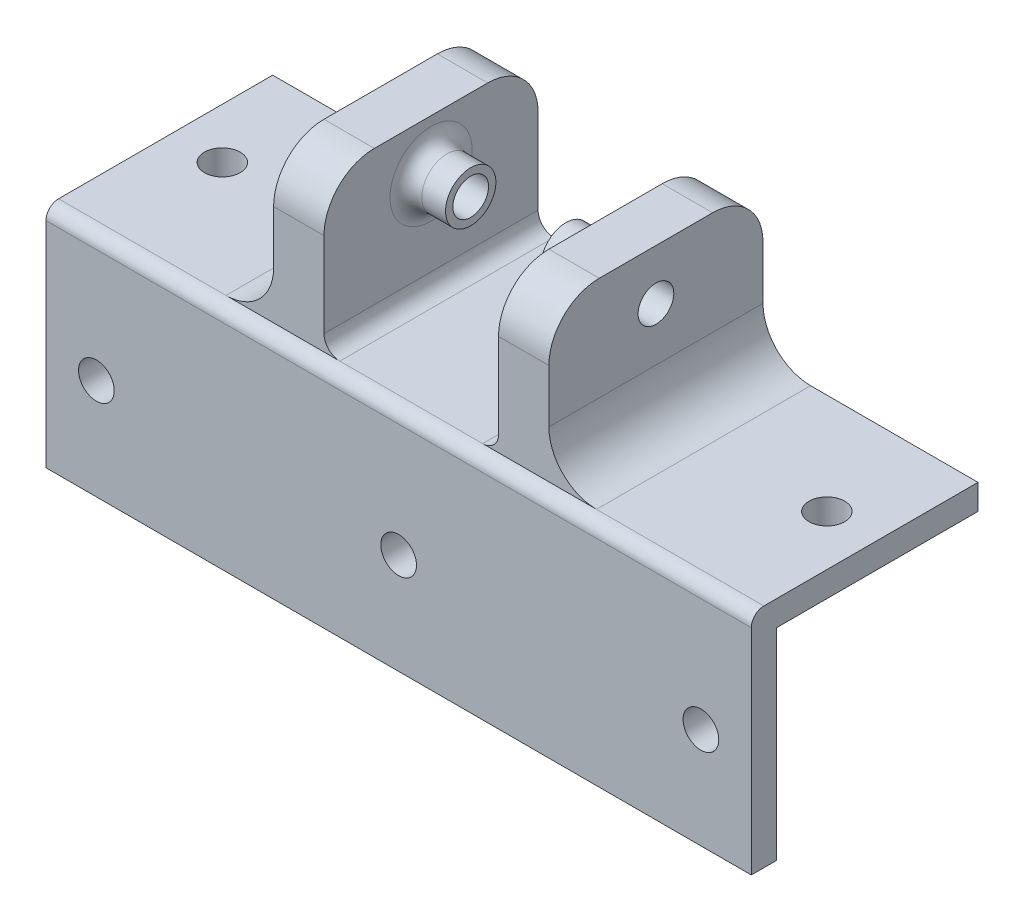
SolidWorks part; units mm, degrees
ref_plane "Front Plane" through (0, 0, 0) normal (0, 0, 1) x (1, 0, 0)
ref_plane "Top Plane" through (0, 0, 0) normal (0, 1, 0) x (1, 0, 0)
ref_plane "Right Plane" through (0, 0, 0) normal (1, 0, 0) x (0, 0, -1)
sketch "Sketch1" plane through (0, 0, 0) normal (0, 0, 1) x (1, 0, 0)
  line L1 (44.45, -12.7) -> (-44.45, -12.7)
  line L2 (44.45, -12.7) -> (44.45, 12.7)
  line L3 (44.45, 12.7) -> (-44.45, 12.7)
  line L4 (-44.45, -12.7) -> (-44.45, 12.7)
  line L5 (44.45, -12.7) -> (-44.45, 12.7) construction
  line L6 (44.45, 12.7) -> (-44.45, -12.7) construction
  circle A0 centre (0, 0) radius 2.25
  circle A1 centre (-38.1, 0) radius 2.25
  circle A2 centre (38.1, 0) radius 2.25
  point P0 (0, 0)
  point P12 (0, 0)
  point P13 (0, 0)
  dimension "D2" = 4.5
  dimension "D1" = 25.4
  dimension "D3" = 38.1
  dimension "D4" = 88.9
  dimension "D5" = 38.1
extrude "Boss-Extrude1" add sketch "Sketch1" along normal blind 3.175
sketch "Sketch2" plane through (0, 12.7, 0) normal (0, 1, 0) x (1, 0, 0)
  line L0 (44.45, 0) -> (-44.45, 0) construction
  line L1 (-44.45, -3.175) -> (44.45, -3.175)
  line L2 (-44.45, -3.175) -> (-44.45, 25.4)
  line L3 (-44.45, 25.4) -> (44.45, 25.4)
  line L4 (44.45, -3.175) -> (44.45, 25.4)
  circle A0 centre (0, 12.7) radius 2.25
  circle A1 centre (-38.1, 12.7) radius 2.25
  circle A2 centre (38.1, 12.7) radius 2.25
  point P14 (0, 12.7)
  point P16 (0, 0)
  dimension "D3" = 4.5
  dimension "D1" = 25.4
  dimension "D2" = 12.7
  dimension "D4" = 38.1
  dimension "D5" = 38.1
extrude "Boss-Extrude2" add sketch "Sketch2" along normal blind 3.175
fillet "Fillet1" radius 1.5875 1 edges at (0, 15.875, 3.175)
sketch "Sketch4" plane through (0, 15.875, 0) normal (0, 1, 0) x (1, 0, 0)
  line L0 (11, 12.7) -> (-11, 12.7)
  line L1 (44.45, 25.4) -> (-44.45, 25.4) construction
  line L2 (-11, 25.4) -> (-17.35, 25.4)
  line L3 (-11, 25.4) -> (-11, -1.5875)
  line L4 (-11, -1.5875) -> (-17.35, -1.5875)
  line L5 (-17.35, 25.4) -> (-17.35, -1.5875)
  line L6 (-44.45, -1.5875) -> (44.45, -1.5875) construction
  line L8 (11, 25.4) -> (17.35, 25.4)
  line L9 (11, 25.4) -> (11, -1.5875)
  line L10 (11, -1.5875) -> (17.35, -1.5875)
  line L11 (17.35, 25.4) -> (17.35, -1.5875)
  line L13 (-11, 12.7) -> (-11, -1.5875)
  line L14 (-11, -1.5875) -> (-17.35, -1.5875)
  line L15 (-17.35, 12.7) -> (-17.35, -1.5875)
  line L17 (11, 12.7) -> (11, -1.5875)
  line L18 (11, -1.5875) -> (17.35, -1.5875)
  line L19 (17.35, 12.7) -> (17.35, -1.5875)
  circle A0 centre (0, 12.7) radius 2.25 construction
  circle A1 centre (0, 12.7) radius 2.25
  point P6 (0, 12.7)
  line M7 (-44.45, -1.5875) -> (44.45, -1.5875)
  line M9 (44.45, 25.4) -> (-44.45, 25.4)
  dimension "D1" = 22
  dimension "D2" = 6.35
  dimension "D3" = 6.35
extrude "Boss-Extrude3" add sketch "Sketch4" along normal blind 19.05 contours L5 L3 M9 M7 | L11 L9 M9 M7 region at (14.175, 15.875, -11.9062) region at (-14.175, 15.875, -11.9062)
sketch "Sketch5" plane through (17.35, 0, 0) normal (1, 0, 0) x (0, 0, -1)
  line L0 (-1.5875, 15.875) -> (25.4, 15.875) construction
  line L1 (25.4, 15.875) -> (-1.5875, 15.875) construction
  circle A0 centre (11.9062, 28.575) radius 2.25
  point P4 (11.9062, 15.875)
  point P5 (0, 0)
  dimension "D1" = 4.5
  dimension "D2" = 12.7
extrude "Cut-Extrude1" cut sketch "Sketch5" against normal blind 100
fillet "Fillet2" radius 6.35 4 edges at (14.175, 34.925, -25.4) (-14.175, 34.925, -25.4) (-14.175, 34.925, 1.5875) (14.175, 34.925, 1.5875)
sketch "Sketch6" plane through (-11, 0, 0) normal (1, 0, 0) x (0, 0, -1)
  circle A0 centre (11.9062, 28.575) radius 3.175
  circle A1 centre (11.9062, 28.575) radius 2.25 construction
  circle A2 centre (11.9062, 28.575) radius 2.25
  dimension "D1" = 6.35
extrude "Boss-Extrude4" add sketch "Sketch6" along normal blind 5
fillet "Fillet3" radius 2 1 edges at (-11, 28.575, -15.0812)
mirror "Mirror2" about plane through (0, 0, 0) normal (1, 0, 0) of bodies 105
fillet "Fillet4" radius 6 2 edges at (17.35, 15.875, -11.9062) (-17.35, 15.875, -11.9062)
fillet "Fillet5" radius 2 2 edges at (11, 15.875, -11.9062) (-11, 15.875, -11.9062)
